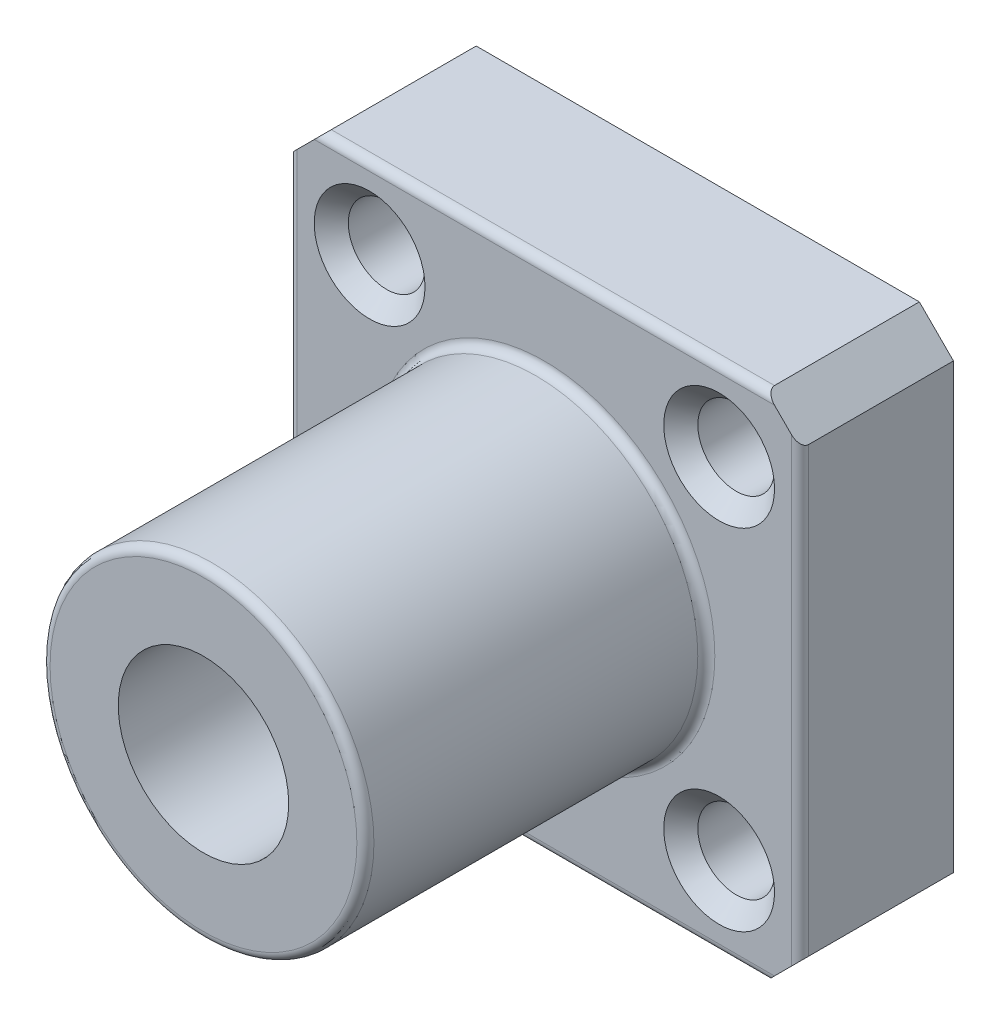
SolidWorks part; units mm, degrees
material "ABS"
ref_plane "Front Plane" through (0, 0, 0) normal (0, 0, 1) x (1, 0, 0)
ref_plane "Top Plane" through (0, 0, 0) normal (0, 1, 0) x (1, 0, 0)
ref_plane "Right Plane" through (0, 0, 0) normal (1, 0, 0) x (0, 0, -1)
sketch "Sketch1" plane through (0, 0, 0) normal (0, 0, 1) x (1, 0, 0)
  line L1 (-15, 15) -> (15, 15)
  line L2 (-15, 15) -> (-15, -15)
  line L3 (-15, -15) -> (15, -15)
  line L4 (15, 15) -> (15, -15)
  line L5 (-15, 15) -> (15, -15) construction
  line L6 (-15, -15) -> (15, 15) construction
  point P0 (0, 0)
  dimension "D1" = 30
  dimension "D2" = 30
extrude "Boss-Extrude1" add sketch "Sketch1" along normal blind 9
sketch "Sketch2" plane through (0, 0, 9) normal (0, 0, 1) x (1, 0, 0)
  circle A0 centre (0, 0) radius 9.5
  dimension "D1" = 19
extrude "Boss-Extrude2" add sketch "Sketch2" along normal blind 20
sketch "Sketch3" plane through (0, 0, 29) normal (0, 0, 1) x (1, 0, 0)
  circle A0 centre (0, 0) radius 5
  dimension "D1" = 10
extrude "Cut-Extrude1" cut sketch "Sketch3" against normal through all
sketch "Sketch4" plane through (0, 0, 0) normal (0, 0, -1) x (-1, 0, 0)
  line L0 (0, 0) -> (-15, 15) construction
  circle A0 centre (-10.253, 10.253) radius 2.25
  circle A1 centre (0, 0) radius 5 construction
  dimension "D1" = 4.5
  dimension "D2" = 14.5
extrude "Cut-Extrude2" cut sketch "Sketch4" against normal through all
chamfer "Chamfer1" distance 1 angle 45 1 edges at (12.503, 10.253, 9)
pattern_circular "CirPattern1" count 4 over 360 about axis through (0, 0, 29) along (0, 0, -1) of "Chamfer1", "Cut-Extrude2"
fillet "Fillet1" radius 0.5 6 edges at (9.5, 0, 9) (9.5, 0, 29) (0, -15, 9) (15, 0, 9) (-15, 0, 9) (0, 15, 9)
chamfer "Chamfer2" distance 2 angle 45 4 edges at (15, -15, 4.25) (-15, -15, 4.25) (15, 15, 4.25) (-15, 15, 4.25)
